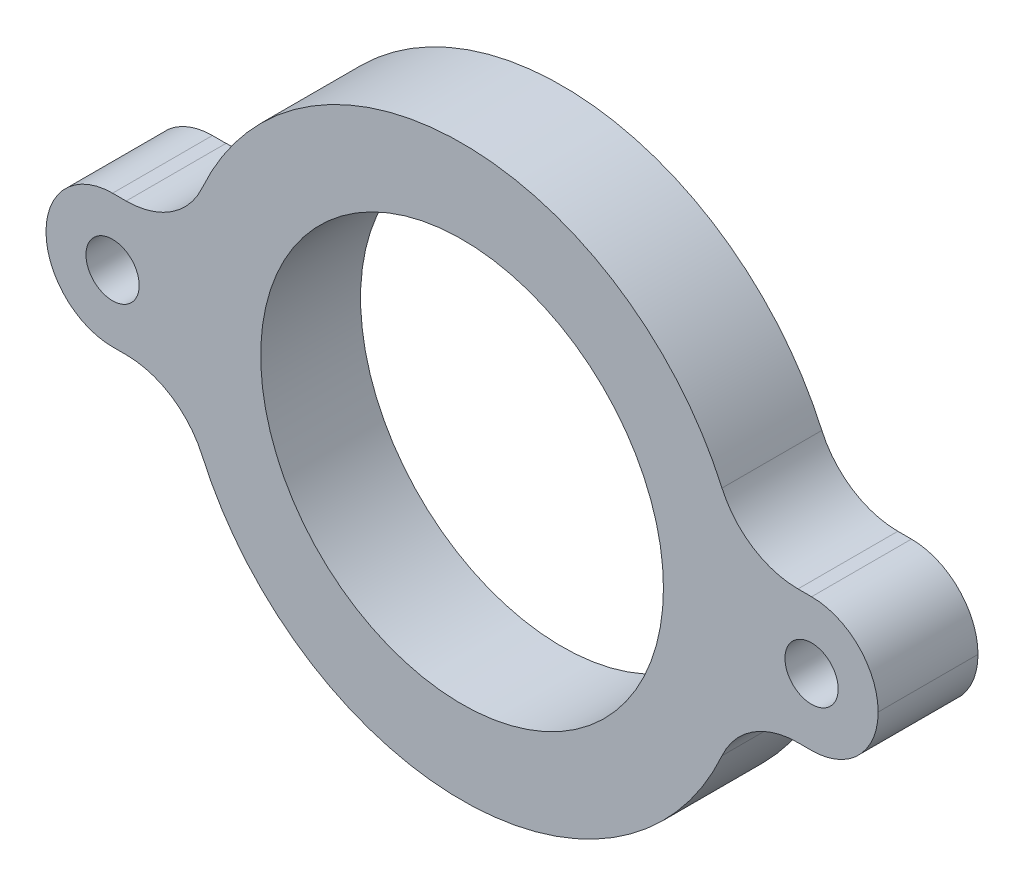
SolidWorks part; units mm, degrees
ref_plane "Plano frontal" through (0, 0, 0) normal (0, 0, 1) x (1, 0, 0)
ref_plane "Plano superior" through (0, 0, 0) normal (0, 1, 0) x (1, 0, 0)
ref_plane "Plano direito" through (0, 0, 0) normal (1, 0, 0) x (0, 0, -1)
sketch "Esboço1" plane through (0, 0, 0) normal (0, 0, 1) x (1, 0, 0)
  line L0 (-19.5214, 0) -> (-12, 0) construction
  line L1 (-21, 0) -> (21, 0) construction
  line L2 (-25, 4) -> (-16.6256, 4)
  line L3 (0, 0) -> (0, 12.1) construction
  line L4 (25, 4) -> (16.6256, 4)
  line L5 (25, -4) -> (16.6256, -4)
  line L6 (-25, -4) -> (-16.6256, -4)
  line L7 (-25, -4) -> (-25, 4)
  line L8 (25, 4) -> (25, -4)
  circle A0 centre (0, 0) radius 12.1
  circle A1 centre (0, 0) radius 12 construction
  circle A3 centre (-21, 0) radius 1.6
  circle A4 centre (21, 0) radius 1.6
  arc A5 (-16.6256, 4) -> (16.6256, 4) centre (0, 0) cw
  arc A6 (-16.6256, -4) -> (16.6256, -4) centre (0, 0) ccw
  circle A7 centre (-13.5, 0) radius 3 construction
  point P5 (-12, 0)
  point P6 (-19.5214, 0)
  point P18 (0, 17.1)
  point P22 (0, 12)
  point P23 (0, 12.1)
  dimension "D1" = 24.2
  dimension "D2" = 24
  dimension "D3" = 3.2
  dimension "D7" = 5
  dimension "D4" = 6
  dimension "D8" = 27
  dimension "D5" = 4
  dimension "D6" = 4
  dimension "D9" = 7.5
extrude "Ressalto-extrusão1" add sketch "Esboço1" along normal blind 6
fillet "Filete2" radius 5 4 edges at (16.6256, 4, 3) (16.6256, -4, 3) (-16.6256, -4, 3) (-16.6256, 4, 3)
fillet "Filete3" radius 4 4 edges at (25, -4, 3) (25, 4, 3) (-25, -4, 3) (-25, 4, 3)
